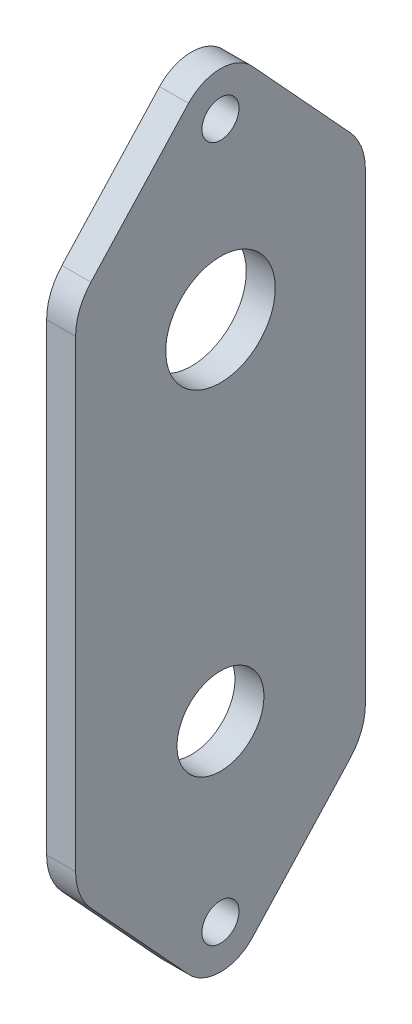
SolidWorks part; units mm, degrees
ref_plane "Front Plane" through (0, 0, 0) normal (0, 0, 1) x (1, 0, 0)
ref_plane "Top Plane" through (0, 0, 0) normal (0, 1, 0) x (1, 0, 0)
ref_plane "Right Plane" through (0, 0, 0) normal (1, 0, 0) x (0, 0, -1)
sketch "Sketch1" plane through (0, 0, 0) normal (1, 0, 0) x (0, 0, -1)
  line L0 (-3.5052, 3.2242) -> (-14.1985, -8.4011)
  line L1 (3.5052, 3.2242) -> (14.1985, -8.4011)
  line L2 (15.875, -12.7) -> (15.875, -63.5)
  line L3 (-15.875, -12.7) -> (-15.875, -63.5)
  line L4 (14.1985, -67.7989) -> (3.5052, -79.4242)
  line L5 (-3.5052, -79.4242) -> (-14.1985, -67.7989)
  line L6 (0, 0) -> (0, -19.05) construction
  line L7 (0, -19.05) -> (0, -57.15) construction
  line L8 (0, -57.15) -> (0, -76.2) construction
  arc A0 (-3.5052, 3.2242) -> (3.5052, 3.2242) centre (0, 0) cw
  arc A1 (-14.1985, -8.4011) -> (-15.875, -12.7) centre (-9.525, -12.7) ccw
  arc A2 (14.1985, -8.4011) -> (15.875, -12.7) centre (9.525, -12.7) cw
  circle A3 centre (0, 0) radius 2.032
  arc A4 (-15.875, -63.5) -> (-14.1985, -67.7989) centre (-9.525, -63.5) ccw
  arc A5 (15.875, -63.5) -> (14.1985, -67.7989) centre (9.525, -63.5) cw
  arc A6 (3.5052, -79.4242) -> (-3.5052, -79.4242) centre (0, -76.2) cw
  circle A7 centre (0, -76.2) radius 2.032
  circle A8 centre (0, -57.15) radius 4.7625
  circle A9 centre (0, -19.05) radius 6
  dimension "D1" = 4.7625
  dimension "D2" = 4.064
  dimension "D5" = 6.35
  dimension "D7" = 12
  dimension "D9" = 9.525
  dimension "D3" = 31.75
  dimension "D4" = 50.8
  dimension "D6" = 76.2
  dimension "D8" = 38.1
extrude "Boss-Extrude1" add sketch "Sketch1" along normal blind 3.175
